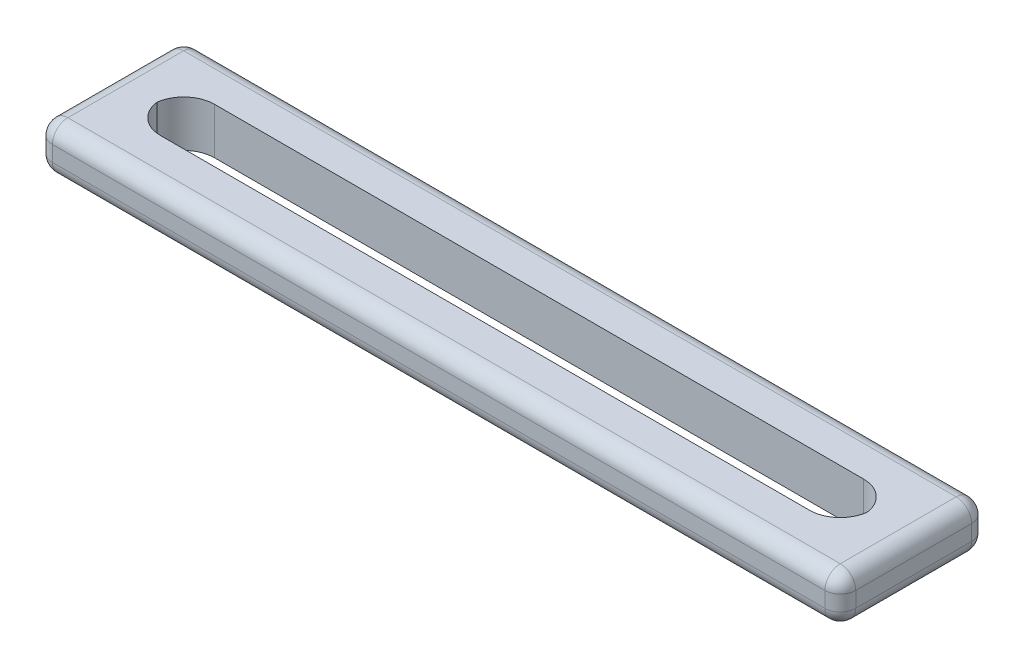
SolidWorks part; units mm, degrees
ref_plane "Front Plane" through (0, 0, 0) normal (0, 0, 1) x (1, 0, 0)
ref_plane "Top Plane" through (0, 0, 0) normal (0, 1, 0) x (1, 0, 0)
ref_plane "Right Plane" through (0, 0, 0) normal (1, 0, 0) x (0, 0, -1)
sketch "Sketch2" plane through (0, 0, 0) normal (0, 1, 0) x (1, 0, 0)
  line L1 (-15.6029, -5.231) -> (36.3971, -5.231)
  line L2 (-15.6029, -5.231) -> (-15.6029, -14.731)
  line L3 (-15.6029, -14.731) -> (36.3971, -14.731)
  line L4 (36.3971, -5.231) -> (36.3971, -14.731)
  line L5 (-12.6029, -8.231) -> (33.3971, -8.231)
  line L6 (-12.6029, -8.231) -> (-12.6029, -11.731)
  line L7 (-12.6029, -11.731) -> (33.3971, -11.731)
  line L8 (33.3971, -8.231) -> (33.3971, -11.731)
  dimension "D1" = 52
  dimension "D2" = 46
  dimension "D3" = 3
  dimension "D4" = 3.5
  dimension "D5" = 3
  dimension "D6" = 3
extrude "Boss-Extrude1" add sketch "Sketch2" along normal blind 3
fillet "Fillet1" radius 2 4 edges at (33.3971, 1.5, 11.731) (33.3971, 1.5, 8.231) (-12.6029, 1.5, 11.731) (-12.6029, 1.5, 8.231)
fillet "Fillet2" radius 1 12 edges at (36.3971, 3, 9.981) (36.3971, 0, 9.981) (10.3971, 3, 14.731) (36.3971, 1.5, 14.731) (10.3971, 0, 14.731) (-15.6029, 3, 9.981) (-15.6029, 1.5, 14.731) (-15.6029, 0, 9.981) (36.3971, 1.5, 5.231) (10.3971, 3, 5.231) (-15.6029, 1.5, 5.231) (10.3971, 0, 5.231)
